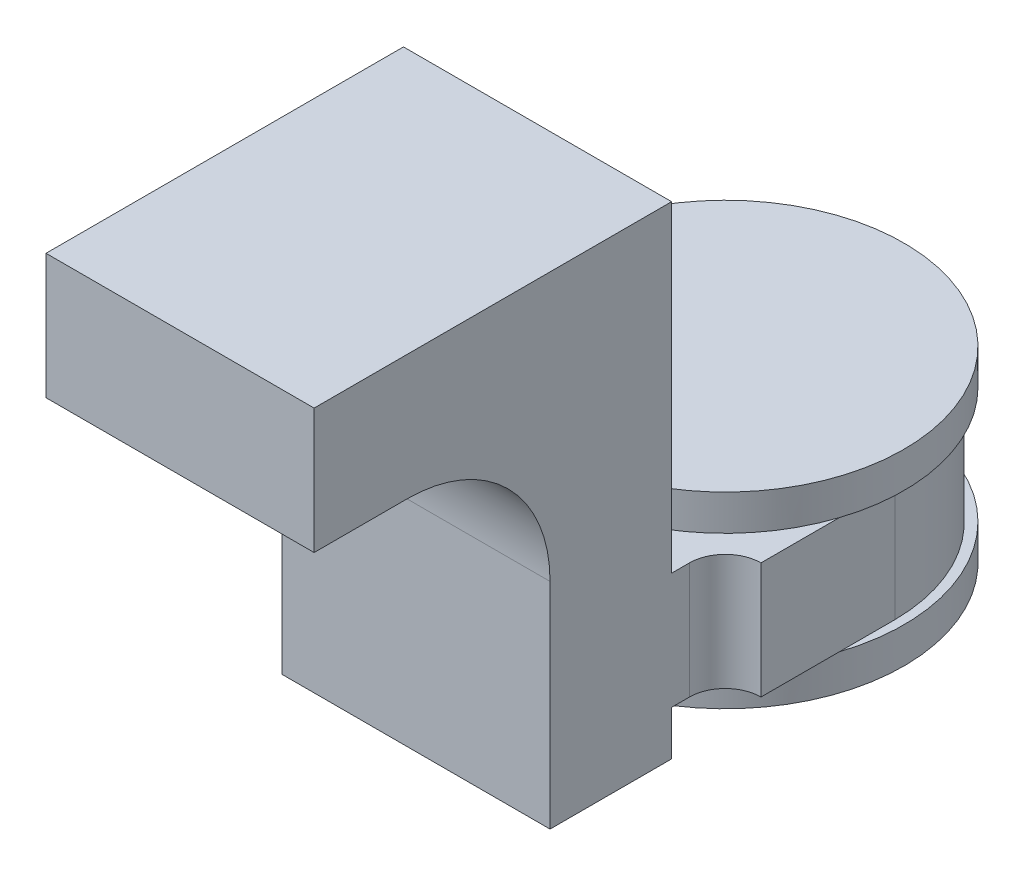
SolidWorks part; units mm, degrees
material "ﾒﾗﾐﾝ樹脂"
ref_plane "正面" through (0, 0, 0) normal (0, 0, 1) x (1, 0, 0)
ref_plane "平面" through (0, 0, 0) normal (0, 1, 0) x (1, 0, 0)
ref_plane "右側面" through (0, 0, 0) normal (1, 0, 0) x (0, 0, -1)
sketch "ｽｹｯﾁ1" plane through (0, 0, 0) normal (0, 1, 0) x (1, 0, 0)
  line L0 (-9.5, 0) -> (-9.5, -7.5)
  line L2 (9.5, 0) -> (9.5, -7.5)
  line L3 (-9.5, -7.5) -> (-8.44, -7.5)
  line L4 (-8.44, -7.5) -> (-8.44, -13.5)
  line L5 (-8.44, -13.5) -> (8.44, -13.5)
  line L6 (8.44, -7.5) -> (8.44, -13.5)
  line L7 (9.5, -7.5) -> (8.44, -7.5)
  arc A0 (-9.5, 0) -> (9.5, 0) centre (0, -0.0613) cw
  point P13 (0, -13.5)
extrude "ﾎﾞｽ - 押し出し2" add sketch "ｽｹｯﾁ1" along normal blind 6.5
sketch "ｽｹｯﾁ3" plane through (0, 6.5, 0) normal (0, 1, 0) x (1, 0, 0)
  circle A0 centre (0, 0) radius 10
extrude "ﾎﾞｽ - 押し出し3" add sketch "ｽｹｯﾁ3" along normal blind 2
sketch "ｽｹｯﾁ4" plane through (0, 0, 0) normal (0, -1, 0) x (1, 0, 0)
  circle A0 centre (0, 0) radius 10
extrude "ﾎﾞｽ - 押し出し4" add sketch "ｽｹｯﾁ4" along normal blind 2
sketch "ｽｹｯﾁ5" plane through (0, -2, 0) normal (0, -1, 0) x (1, 0, 0)
  circle A0 centre (0, 0) radius 5
extrude "ﾎﾞｽ - 押し出し5" add sketch "ｽｹｯﾁ5" along normal blind 1.5
sketch "ｽｹｯﾁ8" plane through (8.44, 0, 0) normal (1, 0, 0) x (0, 0, -1)
  line L1 (-7.5, 6.5) -> (-13.5, 6.5)
  line L2 (-7.5, 6.5) -> (-7.5, 0)
  line L3 (-7.5, 0) -> (-13.5, 0)
  line L4 (-13.5, 6.5) -> (-13.5, 0)
extrude "ｶｯﾄ - 押し出し2" cut sketch "ｽｹｯﾁ8" against normal blind 0.94
sketch "ｽｹｯﾁ9" plane through (-8.44, 0, 0) normal (-1, 0, 0) x (0, 0, 1)
  line L1 (7.5, 6.5) -> (13.5, 6.5)
  line L2 (7.5, 6.5) -> (7.5, 0)
  line L3 (7.5, 0) -> (13.5, 0)
  line L4 (13.5, 6.5) -> (13.5, 0)
extrude "ｶｯﾄ - 押し出し3" cut sketch "ｽｹｯﾁ9" against normal blind 0.94
fillet "ﾌｨﾚｯﾄ4" radius 2 2 edges at (7.5, 3.25, 7.5) (-7.5, 3.25, 7.5)
sketch "ｽｹｯﾁ10" plane through (0, 0, 13.5) normal (0, 0, 1) x (1, 0, 0)
  line L1 (-7.5, 0) -> (7.5, 0)
  line L2 (-7.5, 0) -> (-7.5, -2.5)
  line L3 (-7.5, -2.5) -> (7.5, -2.5)
  line L4 (7.5, 0) -> (7.5, -2.5)
extrude "ﾎﾞｽ - 押し出し6" add sketch "ｽｹｯﾁ10" along normal blind 6.8 separate body
sketch "ｽｹｯﾁ11" plane through (0, 0, 13.5) normal (0, 0, 1) x (1, 0, 0)
  line L2 (-7.5, 6.5) -> (-7.5, 0)
  line L3 (-7.5, 0) -> (7.5, 0)
  line L5 (-7.5, 6.5) -> (7.5, 6.5)
  line L6 (-7.5, 6.5) -> (-7.5, 24.5)
  line L7 (-7.5, 24.5) -> (7.5, 24.5)
  line L8 (7.5, 6.5) -> (7.5, 24.5)
  line M1 (-7.5, 6.5) -> (-7.5, 0)
  line M2 (-7.5, 0) -> (7.5, 0)
  line M3 (7.5, 0) -> (7.5, 6.5)
  line M4 (7.5, 6.5) -> (-7.5, 6.5)
extrude "ﾎﾞｽ - 押し出し7" add sketch "ｽｹｯﾁ11" along normal up to surface (6.8 mm away) contours L8 L7 L6 M4 | M4 M1 M2 M3 region at (0, 3.25, 13.5) region at (0, 15.5, 13.5) up to face at (0, -1.25, 20.3)
sketch "ｽｹｯﾁ12" plane through (0, 0, 20.3) normal (0, 0, 1) x (1, 0, 0)
  line L0 (7.5, -2.5) -> (7.5, 24.5) construction
  line L1 (-7.5, 24.5) -> (7.5, 24.5)
  line L2 (-7.5, 24.5) -> (-7.5, 17.5)
  line L3 (-7.5, 17.5) -> (7.5, 17.5)
  line L4 (7.5, 24.5) -> (7.5, 17.5)
extrude "ﾎﾞｽ - 押し出し8" add sketch "ｽｹｯﾁ12" along normal blind 13.2
sketch "ｽｹｯﾁ16" plane through (0, 0, 13.5) normal (0, 0, -1) x (-1, 0, 0)
  line L1 (-7.5, 24.5) -> (7.5, 24.5)
  line L2 (-7.5, 24.5) -> (-7.5, 6.5)
  line L3 (-7.5, 6.5) -> (7.5, 6.5)
  line L4 (7.5, 24.5) -> (7.5, 6.5)
  line L5 (-7.5, 0) -> (7.5, 0)
  line L6 (-7.5, 0) -> (-7.5, -2.5)
  line L7 (-7.5, -2.5) -> (7.5, -2.5)
  line L8 (7.5, 0) -> (7.5, -2.5)
extrude "ﾎﾞｽ - 押し出し10" add sketch "ｽｹｯﾁ16" along normal blind 3
sketch "ｽｹｯﾁ17" plane through (0, 0, 20.3) normal (0, 0, 1) x (1, 0, 0)
  line L1 (-7.5, 17.5) -> (7.5, 17.5)
  line L2 (-7.5, 17.5) -> (-7.5, -2.5)
  line L3 (-7.5, -2.5) -> (7.5, -2.5)
  line L4 (7.5, 17.5) -> (7.5, -2.5)
extrude "ｶｯﾄ - 押し出し6" cut sketch "ｽｹｯﾁ17" against normal blind 3
sketch "ｽｹｯﾁ18" plane through (0, 0, 33.5) normal (0, 0, 1) x (1, 0, 0)
  line L1 (-7.5, 24.5) -> (7.5, 24.5)
  line L2 (-7.5, 24.5) -> (-7.5, 17.5)
  line L3 (-7.5, 17.5) -> (7.5, 17.5)
  line L4 (7.5, 24.5) -> (7.5, 17.5)
extrude "ｶｯﾄ - 押し出し7" cut sketch "ｽｹｯﾁ18" against normal blind 3
fillet "ﾌｨﾚｯﾄ7" radius 8 1 edges at (0, 17.5, 17.3)
